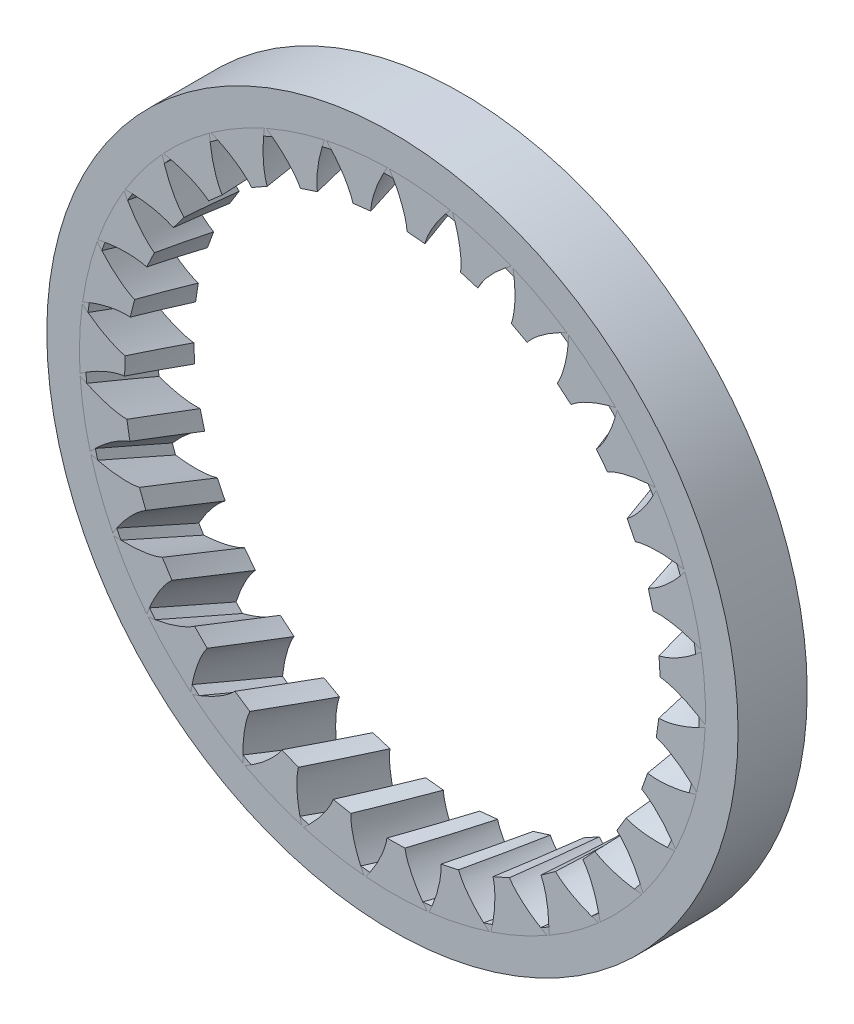
SolidWorks part; units mm, degrees
ref_plane "前视基准面" through (0, 0, 0) normal (0, 0, 1) x (1, 0, 0)
ref_plane "上视基准面" through (0, 0, 0) normal (0, 1, 0) x (1, 0, 0)
ref_plane "右视基准面" through (0, 0, 0) normal (1, 0, 0) x (0, 0, -1)
sketch "草图1" plane through (0, 0, 0) normal (0, 0, 1) x (1, 0, 0)
  circle A0 centre (0, 0) radius 17.7448
  circle A1 centre (0, 0) radius 19.9948
extrude "凸台-拉伸1" add sketch "草图1" along normal blind 4
ref_axis "基准轴1" through (0, 0, -0.2) along (0, 0, 1)
sketch "草图2" plane through (0, 0, 0) normal (0, 0, 1) x (1, 0, 0)
  line L0 (0, 0) -> (0, 15.4948) construction
  arc A0 (0.5184, 15.485) -> (-0.5184, 15.485) centre (0, 0) ccw
  arc A1 (1.775, 18.0194) -> (-1.775, 18.0194) centre (0, 0) ccw
  spline S0 degree 3 poles (0.5184, 15.485) (0.5286, 15.5503) (0.5463, 15.6363) (0.5732, 15.7444) (0.5918, 15.813) (0.6135, 15.8871) (0.6385, 15.9667) (0.667, 16.0516) (0.6993, 16.1417) (0.7356, 16.2369) (0.7761, 16.337) (0.821, 16.442) (0.8705, 16.5516) (0.9249, 16.6658) (0.9843, 16.7844) (1.0489, 16.9072) (1.1189, 17.0341) (1.1945, 17.1649) (1.2759, 17.2994) (1.3633, 17.4375) (1.4568, 17.5789) (1.5922, 17.7751) (1.7, 17.9216) (1.775, 18.0194) knots 0 0 0 0 0.069452 0.092206 0.117116 0.144182 0.173403 0.20478 0.238313 0.274002 0.311846 0.351847 0.394003 0.438314 0.484782 0.533405 0.584184 0.637119 0.69221 0.749456 0.808859 0.870417 1 1 1 1
  spline S1 degree 3 poles (-0.5184, 15.485) (-0.5286, 15.5503) (-0.5463, 15.6363) (-0.5732, 15.7444) (-0.5918, 15.813) (-0.6135, 15.8871) (-0.6385, 15.9667) (-0.667, 16.0516) (-0.6993, 16.1417) (-0.7356, 16.2369) (-0.7761, 16.337) (-0.821, 16.442) (-0.8705, 16.5516) (-0.9249, 16.6658) (-0.9843, 16.7844) (-1.0489, 16.9072) (-1.1189, 17.0341) (-1.1945, 17.1649) (-1.2759, 17.2994) (-1.3633, 17.4375) (-1.4568, 17.5789) (-1.5922, 17.7751) (-1.7, 17.9216) (-1.775, 18.0194) knots 0 0 0 0 0.069452 0.092206 0.117116 0.144182 0.173403 0.20478 0.238313 0.274002 0.311846 0.351847 0.394003 0.438314 0.484782 0.533405 0.584184 0.637119 0.69221 0.749456 0.808859 0.870417 1 1 1 1
sketch "斜齿引导线" plane through (0, 0, 0) normal (0, 0, 1) x (1, 0, 0)
  circle A0 centre (0, 0) radius 16.4948
curve "螺旋线/涡状线1" pitch 284.7475 height 4 radius 16.4948 left hand yes centre (0, 0, 0) axis (0, 0, 1) start towards (0, 1, 0)
sweep "扫描1" add profiles "草图2" path "螺旋线/涡状线1"
pattern_circular "阵列(圆周)1" count 31 every 11.613 about axis through (0, 0, -0.2) along (0, 0, 1) of "扫描1"
sketch "草图4" plane through (0, 0, 0) normal (0, 0, 1) x (1, 0, 0)
  circle A0 centre (0, 0) radius 16.4948 construction
  dimension "Dn" = 32.9895
